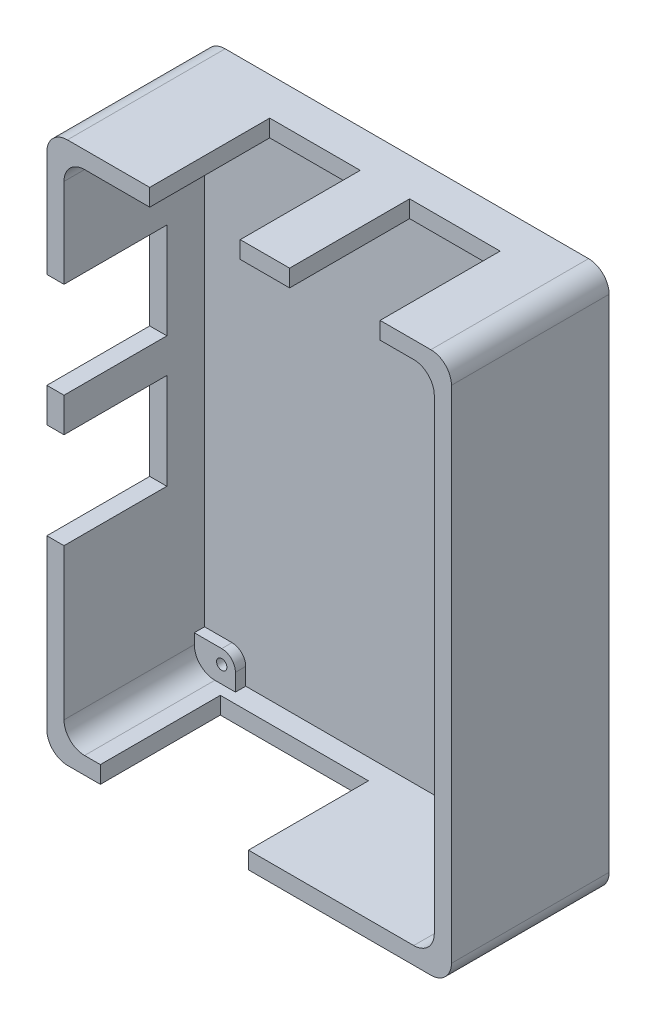
SolidWorks part; units mm, degrees
ref_plane "前视基准面" through (0, 0, 0) normal (0, 0, 1) x (1, 0, 0)
ref_plane "上视基准面" through (0, 0, 0) normal (0, 1, 0) x (1, 0, 0)
ref_plane "右视基准面" through (0, 0, 0) normal (1, 0, 0) x (0, 0, -1)
sketch "草图1" plane through (0, 0, 0) normal (0, 0, 1) x (1, 0, 0)
  line L0 (-23, 31.5) -> (23, 31.5) construction
  line L1 (-26.5, 39.5) -> (26.5, 39.5)
  line L2 (-29.5, 36.5) -> (-29.5, -36.5)
  line L3 (-26.5, -39.5) -> (26.5, -39.5)
  line L4 (29.5, 36.5) -> (29.5, -36.5)
  line L5 (-29.5, 39.5) -> (29.5, -39.5) construction
  line L6 (-29.5, -39.5) -> (29.5, 39.5) construction
  line L7 (-24, 37) -> (24, 37)
  line L8 (-27, 34) -> (-27, -34)
  line L9 (-24, -37) -> (24, -37)
  line L10 (27, 34) -> (27, -34)
  line L11 (-27, 37) -> (27, -37) construction
  line L12 (-27, -37) -> (27, 37) construction
  line L13 (23, 31.5) -> (23, -34.5) construction
  line L14 (23, -34.5) -> (-23, -34.5) construction
  line L15 (-23, -34.5) -> (-23, 31.5) construction
  line L16 (-29.5, 21) -> (-27, 21)
  line L17 (-29.5, 7) -> (-27, 7)
  line L18 (-29.5, 2) -> (-27, 2)
  line L19 (-29.5, -12) -> (-27, -12)
  line L20 (-14.5, 39.5) -> (-14.5, 37)
  line L21 (-1.3, 39.5) -> (-1.3, 37)
  line L22 (5.9, 39.5) -> (5.9, 37)
  line L23 (19.1, 39.5) -> (19.1, 37)
  line L24 (-21.7, -37) -> (-21.7, -39.5)
  line L25 (-0.1, -37) -> (-0.1, -39.5)
  line L26 (-27, 29.5) -> (-23, 29.5)
  line L27 (-21, 31.5) -> (-21, 37)
  line L28 (21, 37) -> (21, 31.5)
  line L29 (23, 29.5) -> (27, 29.5)
  line L30 (21, -34.5) -> (21, -37)
  line L31 (23, -32.5) -> (27, -32.5)
  line L32 (-27, -32.5) -> (-23, -32.5)
  line L33 (-21, -34.5) -> (-21, -37)
  circle A0 centre (-23, 31.5) radius 0.75
  circle A1 centre (23, 31.5) radius 0.75
  circle A2 centre (23, -34.5) radius 0.75
  circle A3 centre (-23, -34.5) radius 0.75
  arc A4 (-27, 34) -> (-24, 37) centre (-24, 34) cw
  arc A5 (24, 37) -> (27, 34) centre (24, 34) cw
  arc A6 (27, -34) -> (24, -37) centre (24, -34) cw
  arc A7 (-24, -37) -> (-27, -34) centre (-24, -34) cw
  arc A8 (-29.5, -36.5) -> (-26.5, -39.5) centre (-26.5, -36.5) ccw
  arc A9 (26.5, -39.5) -> (29.5, -36.5) centre (26.5, -36.5) ccw
  arc A10 (29.5, 36.5) -> (26.5, 39.5) centre (26.5, 36.5) ccw
  arc A11 (-29.5, 36.5) -> (-26.5, 39.5) centre (-26.5, 36.5) cw
  arc A12 (-23, 29.5) -> (-21, 31.5) centre (-23, 31.5) ccw
  arc A13 (21, 31.5) -> (23, 29.5) centre (23, 31.5) ccw
  arc A14 (21, -34.5) -> (23, -32.5) centre (23, -34.5) cw
  arc A15 (-21, -34.5) -> (-23, -32.5) centre (-23, -34.5) ccw
  point P0 (0, 0)
  point P6 (0, 0)
  point P11 (-23, 31.5)
  point P12 (23, 31.5)
  point P13 (23, -34.5)
  point P14 (-23, -34.5)
  dimension "D7" = 1.5
  dimension "D22" = 3
  dimension "D25" = 2
  dimension "D28" = 2
  dimension "D30" = 2
  dimension "D31" = 2
  dimension "D34" = 2
  dimension "D3" = 2.5
  dimension "D4" = 2.5
  dimension "D5" = 46
  dimension "D6" = 66
  dimension "D8" = 4
  dimension "D9" = 4
  dimension "D10" = 2.5
  dimension "D11" = 5.5
  dimension "D12" = 14
  dimension "D13" = 14
  dimension "D14" = 5
  dimension "D15" = 10.5
  dimension "D16" = 13.2
  dimension "D17" = 13.2
  dimension "D18" = 7.2
  dimension "D19" = 3.9
  dimension "D20" = 21.6
  dimension "D21" = 1.3
  dimension "D23" = 2
  dimension "D24" = 2
  dimension "D26" = 2
  dimension "D27" = 2
  dimension "D29" = 2
  dimension "D32" = 2
  dimension "D33" = 2
  dimension "D35" = 54
  dimension "D36" = 68
extrude "凸台-拉伸1" add sketch "草图1" against normal blind 2.5 contours L1 A10 L4 A9 L3 A8 L2 A11
extrude "凸台-拉伸3" add sketch "草图1<5>" along normal blind 1.5 contours L26 A12 L27 L7 A4 L8 A0 | A14 L30 L9 A6 L10 L31 A2 | L33 A15 L32 L8 A7 L9 A3 | L28 A13 L29 L10 A5 L7 A1 region at (-23.9866, 33.2495, 0) region at (23.9866, 33.2495, 0) region at (-23.9759, -34.7027, 0) region at (23.9759, -34.7027, 0)
sketch "草图1<5>" plane through (0, 0, 0) normal (0, 0, 1) x (1, 0, 0) same geometry as "草图1"
extrude "凸台-拉伸4" add sketch "草图1<6>" along normal blind 3 contours L21 L1 L20 L7 | L23 L1 L22 L7 | L25 L9 L24 L3 region at (-7.9, 38.25, 0) region at (12.5, 38.25, 0) region at (-10.9, -38.25, 0)
sketch "草图1<6>" plane through (0, 0, 0) normal (0, 0, 1) x (1, 0, 0) same geometry as "草图1"
extrude "凸台-拉伸5" add sketch "草图1<7>" along normal blind 5.5 contours L2 L17 L8 L16 | L2 L19 L8 L18 region at (-28.25, 14, 0) region at (-28.25, -5, 0)
sketch "草图1<7>" plane through (0, 0, 0) normal (0, 0, 1) x (1, 0, 0) same geometry as "草图1"
extrude "凸台-拉伸6" add sketch "草图1<8>" along normal blind 20.5 contours L4 A10 L1 L23 L7 A5 L10 A6 L9 L25 L3 A9 | L22 L1 L21 L7 | A11 L2 L16 L8 A4 L7 L20 L1 | L2 L18 L8 L17 | L2 A8 L3 L24 L9 A7 L8 L19 region at (-20.5, 39.2618, 0) region at (2.3, 38.25, 0) region at (-28.25, 4.5, 0) region at (22.8, 38.6564, 0) region at (-27.5609, -27.7109, 0)
sketch "草图1<8>" plane through (0, 0, 0) normal (0, 0, 1) x (1, 0, 0) same geometry as "草图1"
extrude "切除-拉伸1" cut sketch "草图1<9>" against normal blind 1.4 contours A0 | A1 | A2 | A3
sketch "草图1<9>" plane through (0, 0, 0) normal (0, 0, 1) x (1, 0, 0) same geometry as "草图1"
